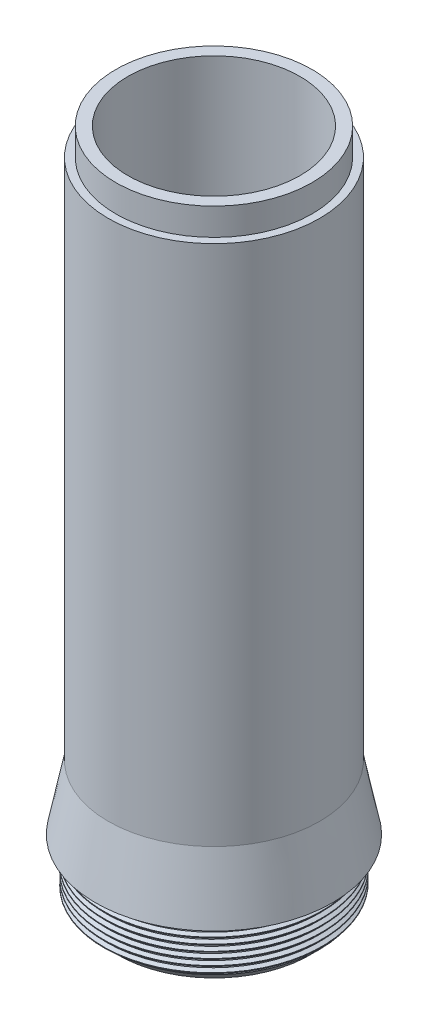
SolidWorks part; units mm, degrees
ref_plane "Front Plane" through (0, 0, 0) normal (0, 0, 1) x (1, 0, 0)
ref_plane "Top Plane" through (0, 0, 0) normal (0, 1, 0) x (1, 0, 0)
ref_plane "Right Plane" through (0, 0, 0) normal (1, 0, 0) x (0, 0, -1)
sketch "Sketch1" plane through (0, 0, 0) normal (0, 0, 1) x (1, 0, 0)
  line L0 (0, -527.2215) -> (0, 25833.8527) construction
  line L2 (-21.45, -9.5337) -> (-21.45, 1.9663)
  line L5 (-21.45, 1.9663) -> (-24.05, 1.9663)
  line L8 (-21.45, 14.9663) -> (-21.45, 117.9663)
  line L10 (-21.45, 14.9663) -> (-24.05, 1.9663)
  line L16 (-19.9, 120.8952) -> (-19.9, 126.3952)
  line L17 (-19.9, 126.3952) -> (-17.45, 126.3952)
  line L19 (-17.45, 126.3952) -> (-17.45, -9.5337)
  line L20 (-21.45, 117.9663) -> (-21.45, 120.8952)
  line L21 (-21.45, 120.8952) -> (-19.9, 120.8952)
  line L22 (-21.45, -9.5337) -> (-17.45, -9.5337)
  dimension "D2" = 11.5
  dimension "D3" = 5.5
  dimension "D7" = 48.1
  dimension "D13" = 24.5
  dimension "D14" = 13.2575
revolve "Revolve1" add sketch "Sketch1" angle 360 about L0
thread "Thread1" pitch 1.25 method extrude profile "Thread Profile1" start angle 0, offset 0, length 9, pitch 1.25, diameter 42.9
ref_plane "Plane1" through (-21.45, 1.9663, 0) normal (0, 0, 1) x (-1, 0, 0)
sketch "Thread Profile1" plane through (-21.45, 1.9663, 0) normal (0, 0, 1) x (-1, 0, 0)
  line L0 (0, 0) -> (0, 1.25) construction
  line L1 (0, 0) -> (0.6766, 0.3906)
  line L2 (0.6766, 0.3906) -> (0.6766, 0.5469)
  line L3 (0.6766, 0.5469) -> (0, 0.9375)
  line L4 (0.6766, 0.4687) -> (0, 0.4687) construction
  line L11 (0, 0) -> (0, 0.9375)
  point P2 (0, 0)
  dimension "Pitch" = 1.25
  dimension "Profile_Angle" = 60
  dimension "Profile_Land" = 0.1562
  dimension "Profile_Height" = 0.6766
fillet "Chamfer1" radius 2 1 edges at (21.45, -9.5337, 0) type face fillet profile chamfer first side face at (21.45, -9.5337, 0) second side face at (17.45, -9.5337, 0)
